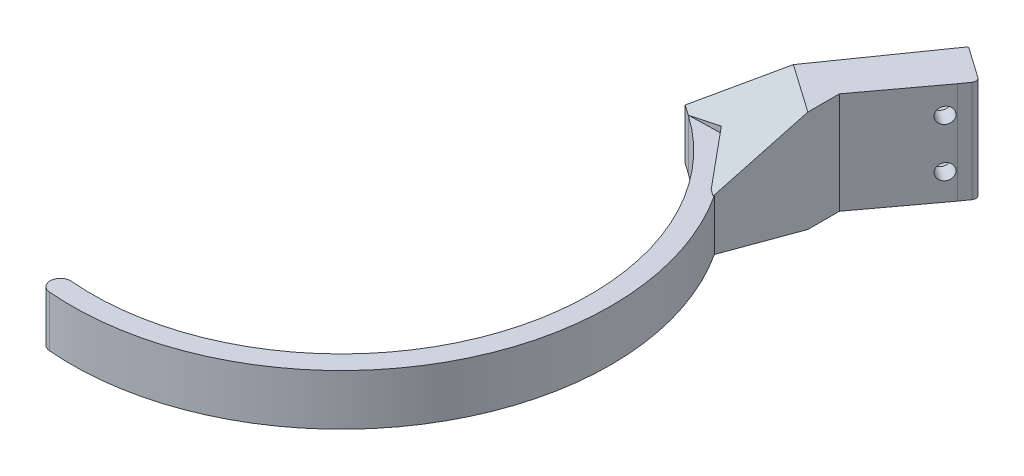
SolidWorks part; units mm, degrees
ref_plane "前视基准面" through (0, 0, 0) normal (0, 0, 1) x (1, 0, 0)
ref_plane "上视基准面" through (0, 0, 0) normal (0, 1, 0) x (1, 0, 0)
ref_plane "右视基准面" through (0, 0, 0) normal (1, 0, 0) x (0, 0, -1)
sketch "草图1" plane through (0, 0, 0) normal (0, 1, 0) x (1, 0, 0)
  line L0 (-9.6017, 8.1958) -> (13.3414, 40.9619)
  line L9 (13.3414, 40.9619) -> (19.485, 36.6601)
  line L10 (19.7306, 35.2673) -> (18.5464, 33.5762)
  line L11 (18.5464, 33.5762) -> (-3.458, 3.894)
  line L12 (-3.458, 3.894) -> (-9.6017, 8.1958)
  line L13 (-9.6017, 8.1958) -> (-7.5538, 6.7619)
  line L15 (-7.881, 10.6533) -> (-5.8331, 9.2193)
  line L16 (-8.4545, 9.8341) -> (-6.4067, 8.4002)
  line L17 (-9.0281, 9.015) -> (-6.9802, 7.581)
  line L18 (-65.485, -75.9725) -> (-64.9114, -75.1533)
  line L19 (-3.458, 3.894) -> (-4.4236, 2.515)
  line L20 (-64.7372, -78.8778) -> (-64.7372, -78.8778)
  line L21 (-7.3074, 11.4724) -> (-5.2595, 10.0385)
  line L22 (-63.7643, -73.515) -> (-66.0586, -76.7916)
  arc A1 (19.7306, 35.2673) -> (19.485, 36.6601) centre (18.9114, 35.8409) ccw
  arc A3 (-7.5538, 6.7619) -> (-63.7643, -73.515) centre (-35.6591, -33.3766) cw
  arc A4 (-5.2595, 10.0385) -> (-66.0586, -76.7916) centre (-35.6591, -33.3766) cw
  arc A5 (-6.4067, 8.4002) -> (-66.0586, -76.7916) centre (-36.2326, -34.1957) cw construction
  arc A6 (-6.9802, 7.581) -> (-65.485, -75.9725) centre (-36.2326, -34.1957) cw construction
  arc A7 (-7.5538, 6.7619) -> (-64.9114, -75.1533) centre (-36.2326, -34.1957) cw construction
  arc A8 (-5.8331, 9.2193) -> (-64.7372, -78.8778) centre (-36.2326, -34.1957) cw construction
  dimension "D1" = 2
  dimension "D3" = 1
  dimension "D6" = 3
  dimension "D8" = 4
  dimension "D2" = 1
  dimension "D4" = 7.5
  dimension "D5" = 40
  dimension "D7" = 2.5
extrude "凸台-拉伸5" add sketch "草图1" along normal blind 20 contours L17 L12 L11 L10 A1 L9 L0 | L17 L0 L12 | L12 | L18 | L12 region at (-5.4026, 0, -7.67) region at (-4.5254, 0, -4.5478) region at (-1.3346, 0, -4.6571) region at (6.5158, 0, -24.1514)
sketch "草图4" plane through (-10.2936, 0, -7.2077) normal (-0.8192, 0, -0.5736) x (-0.5736, 0, 0.8192)
  line L0 (-41.2063, 20) -> (-41.2063, 10)
  line L2 (-41.2063, 20) -> (-41.2063, 0) construction
  line L3 (-41.2063, 10) -> (-36.4063, 10)
  line L6 (-36.4063, 10) -> (-36.4063, 14.8)
  line L13 (-36.4063, 10) -> (-36.4063, 5.2)
  line L17 (-34.7155, 11.8429) -> (-33, 14.7858)
  line L18 (-33, 14.7858) -> (-34.6908, 17.7429)
  line L19 (-34.6908, 17.7429) -> (-38.0972, 17.7571)
  line L20 (-38.0972, 17.7571) -> (-39.8127, 14.8142)
  line L21 (-39.8127, 14.8142) -> (-38.1218, 11.8571)
  line L22 (-38.1218, 11.8571) -> (-34.7155, 11.8429)
  line L23 (-34.6118, 2.3046) -> (-33.0016, 5.3064)
  line L24 (-33.0016, 5.3064) -> (-34.7961, 8.2018)
  line L25 (-34.7961, 8.2018) -> (-38.2008, 8.0954)
  line L26 (-38.2008, 8.0954) -> (-39.811, 5.0936)
  line L27 (-39.811, 5.0936) -> (-38.0165, 2.1982)
  line L28 (-38.0165, 2.1982) -> (-34.6118, 2.3046)
  circle A6 centre (-36.4063, 14.8) radius 1.55
  circle A7 centre (-36.4063, 5.2) radius 1.55
  circle A8 centre (-36.4063, 14.8) radius 2.95 construction
  circle A9 centre (-36.4063, 5.2) radius 2.95 construction
  dimension "D2" = 4.8
  dimension "D1" = 10
  dimension "D3" = 4.8
extrude "切除-拉伸1" cut sketch "草图4" against normal blind 10 contours A6 | A7 region at (11.1991, 15.865, -37.9024) region at (9.9773, 6.265, -36.1576)
extrude "切除-拉伸2" cut sketch "草图4<4>" against normal blind 5 contours L19 L20 L21 L22 L17 L18 | L25 L26 L27 L28 L23 L24
sketch "草图4<4>" plane through (-10.2936, 0, -7.2077) normal (-0.8192, 0, -0.5736) x (-0.5736, 0, 0.8192) same geometry as "草图4"
sketch "草图5" plane through (0, 20, 0) normal (0, 1, 0) x (1, 0, 0)
  line L0 (-63.7643, -73.515) -> (-66.0586, -76.7916)
  line L1 (-7.5538, 6.7619) -> (-1.2216, 6.9107)
  arc A0 (-63.7643, -73.515) -> (-7.5538, 6.7619) centre (-35.6591, -33.3766) ccw
  arc A1 (-66.0586, -76.7916) -> (-5.2595, 10.0385) centre (-35.6591, -33.3766) ccw
  arc M2 (-7.5538, 6.7619) -> (-63.7643, -73.515) centre (-35.6591, -33.3766) cw
  line M3 (-63.7643, -73.515) -> (-66.0586, -76.7916)
  arc M4 (-66.0586, -76.7916) -> (-1.2216, 6.9107) centre (-35.6591, -33.3766) ccw
  dimension "D1" = 4
extrude "切除-拉伸3" cut sketch "草图5" against normal blind 5 contours L1 M2 M3 M4 region at (5.5044, 20, 62.1996)
sketch "草图6" plane through (0, 0, 0) normal (0, -1, 0) x (1, 0, 0)
  line L0 (-66.0586, 76.7916) -> (-63.7643, 73.515)
  line L1 (-7.5538, -6.7619) -> (-1.2216, -6.9107)
  arc A0 (-63.7643, 73.515) -> (-7.5538, -6.7619) centre (-35.6591, 33.3766) cw
  arc A1 (-66.0586, 76.7916) -> (-5.2595, -10.0385) centre (-35.6591, 33.3766) cw
  arc M7 (-1.2216, -6.9107) -> (-66.0586, 76.7916) centre (-35.6591, 33.3766) ccw
  line M8 (-66.0586, 76.7916) -> (-63.7643, 73.515)
  arc M9 (-63.7643, 73.515) -> (-7.5538, -6.7619) centre (-35.6591, 33.3766) cw
  dimension "D1" = 4
extrude "切除-拉伸4" cut sketch "草图6" against normal blind 5 contours L1 M9 M7 M8 region at (5.2515, 0, 65.0665)
sketch "草图7" plane through (-10.2936, 0, -7.2077) normal (-0.8192, 0, -0.5736) x (-0.5736, 0, 0.8192)
  line L0 (-1.2063, 5) -> (-16.4736, 0)
  line L1 (-1.2063, 0) -> (-41.2063, 0) construction
  line L4 (-1.2063, 20) -> (-16.4736, 20)
  line L5 (-1.2063, 20) -> (-41.2063, 20) construction
  line L6 (-16.4736, 20) -> (-1.2063, 15)
  line L8 (-1.2063, 20) -> (28.5726, 20)
  line L11 (-16.4736, 0) -> (0, 0)
  line L12 (-1.2063, 15) -> (28.5726, 15)
  line L13 (96.7937, 15) -> (-1.2063, 15) construction
  line L14 (28.5726, 15) -> (28.5726, 20)
  line L15 (-1.2063, 5) -> (28.5726, 5)
  line L16 (-1.2063, 5) -> (96.7937, 5) construction
  line L17 (28.5726, 5) -> (28.5726, 0)
  line L18 (28.5726, 0) -> (0, 0)
sketch "草图9" plane through (0, 0, 0) normal (0, 1, 0) x (1, 0, 0)
  line L0 (8.6624, 20.2434) -> (-1.2216, 6.9107)
  line L1 (18.5464, 33.5762) -> (-1.2216, 6.9107) construction
  line L2 (-1.2216, 6.9107) -> (8.6624, -5.2758)
  line L3 (8.6624, -5.2758) -> (8.6624, 20.2434)
extrude "凸台-拉伸7" add sketch "草图9" along normal blind 20
extrude "切除-拉伸6" cut sketch "草图7" against normal blind 30
sketch "草图11" plane through (0, 15, 0) normal (0, 1, 0) x (1, 0, 0)
  line L0 (-63.7643, -73.515) -> (-66.0586, -76.7916)
  line L1 (-39.9297, -82.1901) -> (-40.2783, -86.1749)
  circle A1 centre (-34.4817, -37.2847) radius 1
  arc A2 (-63.7643, -73.515) -> (-39.9297, -82.1901) centre (-35.6591, -33.3766) ccw
  arc A3 (-63.7643, -73.515) -> (-7.5538, 6.7619) centre (-35.6591, -33.3766) ccw construction
  arc A4 (-66.0586, -76.7916) -> (-40.2783, -86.1749) centre (-35.6591, -33.3766) ccw
  arc A5 (-66.0586, -76.7916) -> (8.6624, -4.3144) centre (-35.6591, -33.3766) ccw construction
extrude "切除-拉伸7" cut sketch "草图11" against normal blind 10
sketch "草图18" plane through (0, 15, 0) normal (0, 1, 0) x (1, 0, 0)
  line L0 (-40.2783, -86.1749) -> (-39.9297, -82.1901)
  arc A0 (-39.9297, -82.1901) -> (-40.2783, -86.1749) centre (-40.104, -84.1825) ccw
  line M1 (-39.9297, -82.1901) -> (-40.2783, -86.1749)
extrude "凸台-拉伸8" add sketch "草图18" against normal blind 10 contours A0 M1 region at (-40.9496, 15, 84.1085)
